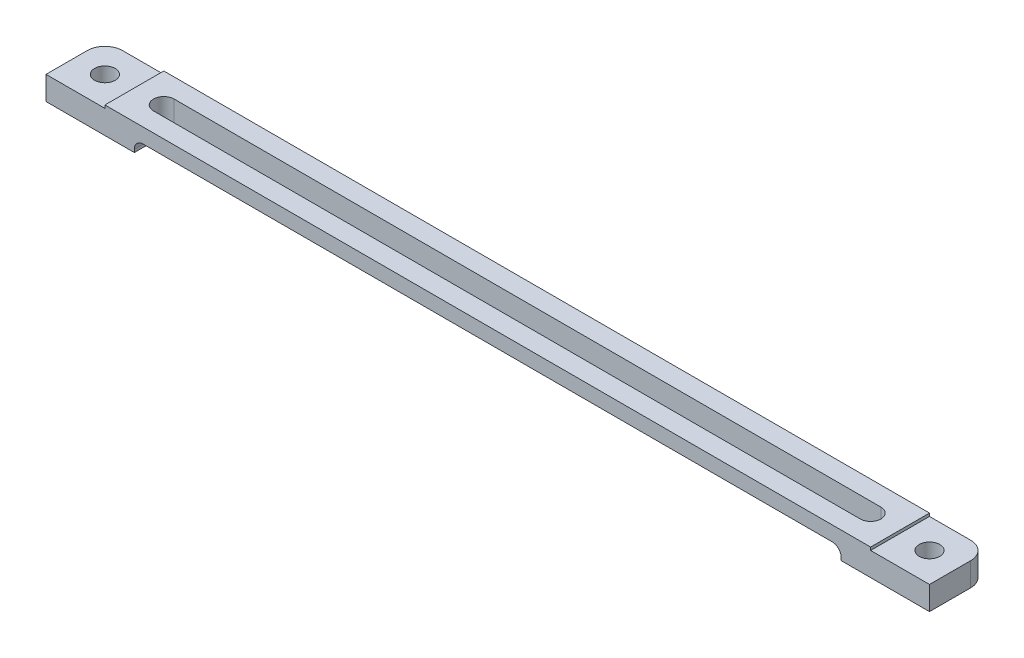
SolidWorks part; units mm, degrees
ref_plane "Front Plane" through (0, 0, 0) normal (0, 0, 1) x (1, 0, 0)
ref_plane "Top Plane" through (0, 0, 0) normal (0, 1, 0) x (1, 0, 0)
ref_plane "Right Plane" through (0, 0, 0) normal (1, 0, 0) x (0, 0, -1)
sketch "Sketch1" plane through (0, 0, 0) normal (0, 1, 0) x (1, 0, 0)
  line L1 (72, 5) -> (-72, 5)
  line L2 (75, 2) -> (75, -5)
  line L3 (75, -5) -> (-75, -5)
  line L4 (-75, 2) -> (-75, -5)
  line L5 (75, 5) -> (-75, -5) construction
  line L6 (75, -5) -> (-75, 5) construction
  line L7 (60, -1.75) -> (-60, -1.75)
  line L8 (60, -1.75) -> (60, 1.75)
  line L9 (60, 1.75) -> (-60, 1.75)
  line L10 (-60, -1.75) -> (-60, 1.75)
  line L11 (60, -1.75) -> (-60, 1.75) construction
  line L12 (60, 1.75) -> (-60, -1.75) construction
  circle A0 centre (-70, 0) radius 1.75
  circle A1 centre (70, 0) radius 1.75
  arc A2 (75, 2) -> (72, 5) centre (72, 2) ccw
  arc A3 (-72, 5) -> (-75, 2) centre (-72, 2) ccw
  circle A4 centre (-60, 0) radius 1.75
  circle A5 centre (60, 0) radius 1.75
  point P0 (0, 0)
  point P16 (0, 0)
  dimension "D3" = 3.5
  dimension "D6" = 3.5
  dimension "D9" = 3
  dimension "D10" = 3
  dimension "D1" = 10
  dimension "D2" = 150
  dimension "D4" = 5
  dimension "D5" = 5
  dimension "D7" = 5
  dimension "D8" = 5
  dimension "D11" = 3.5
  dimension "D12" = 120
extrude "Boss-Extrude1" add sketch "Sketch1" along normal blind 4 contours L1 A3 L4 L3 L2 A2 A5 L7 A4 L9 A0 A1 region at (73.0583, 0, -3.0583)
sketch "Sketch2" plane through (0, 4, 0) normal (0, 1, 0) x (1, 0, 0)
  line L0 (72, 5) -> (-72, 5) construction
  line L1 (-65, 5) -> (65, 5)
  line L2 (-65, 5) -> (-65, -5)
  line L3 (-65, -5) -> (65, -5)
  line L4 (65, 5) -> (65, -5)
  line L5 (75, -5) -> (-75, -5) construction
  line L6 (-75, 2) -> (-75, -5) construction
  line L7 (75, 2) -> (75, -5) construction
  line L12 (72, 5) -> (-72, 5)
  line L13 (-75, 2) -> (-75, -5)
  line L14 (-75, -5) -> (75, -5)
  line L15 (75, -5) -> (75, 2)
  line L16 (72, 5) -> (-72, 5)
  line L17 (-75, 2) -> (-75, -5)
  line L18 (-75, -5) -> (75, -5)
  line L19 (75, -5) -> (75, 2)
  arc A2 (-72, 5) -> (-75, 2) centre (-72, 2) ccw
  arc A3 (75, 2) -> (72, 5) centre (72, 2) ccw
  arc A4 (-72, 5) -> (-75, 2) centre (-72, 2) ccw
  arc A5 (75, 2) -> (72, 5) centre (72, 2) ccw
  arc M11 (60, 1.75) -> (60, -1.75) centre (60, 0) cw
  line M12 (60, -1.75) -> (-60, -1.75)
  arc M13 (-60, -1.75) -> (-60, 1.75) centre (-60, 0) cw
  line M14 (-60, 1.75) -> (60, 1.75)
  line M17 (72, 5) -> (-72, 5)
  line M20 (-75, -5) -> (75, -5)
  dimension "D1" = 10
  dimension "D2" = 10
  dimension "D3" = 0
extrude "Boss-Extrude2" add sketch "Sketch2" along normal blind 0.5 contours L4 L2 M17 M20 M14 M11 M12 M13 region at (0, 4, -3.6962)
sketch "Sketch3" plane through (0, 0, 5) normal (0, 0, 1) x (1, 0, 0)
  line L0 (0, 0) -> (0, 4.5) construction
  line L1 (-65, 4.5) -> (65, 4.5) construction
  line L2 (75, 0) -> (-75, 0) construction
  line L3 (-58.5, 2) -> (58.5, 2)
  line L4 (-60, 0.5) -> (-60, 0)
  line L5 (-60, 0) -> (60, 0)
  line L6 (60, 0.5) -> (60, 0)
  line L7 (-60, 2) -> (60, 0) construction
  line L8 (-60, 0) -> (60, 2) construction
  arc A0 (58.5, 2) -> (60, 0.5) centre (58.5, 0.5) cw
  arc A1 (-58.5, 2) -> (-60, 0.5) centre (-58.5, 0.5) ccw
  point P5 (0, 1)
  dimension "D3" = 1.5
  dimension "D4" = 1.5
  dimension "D1" = 2
  dimension "D2" = 120
extrude "Cut-Extrude1" cut sketch "Sketch3" against normal blind 2
